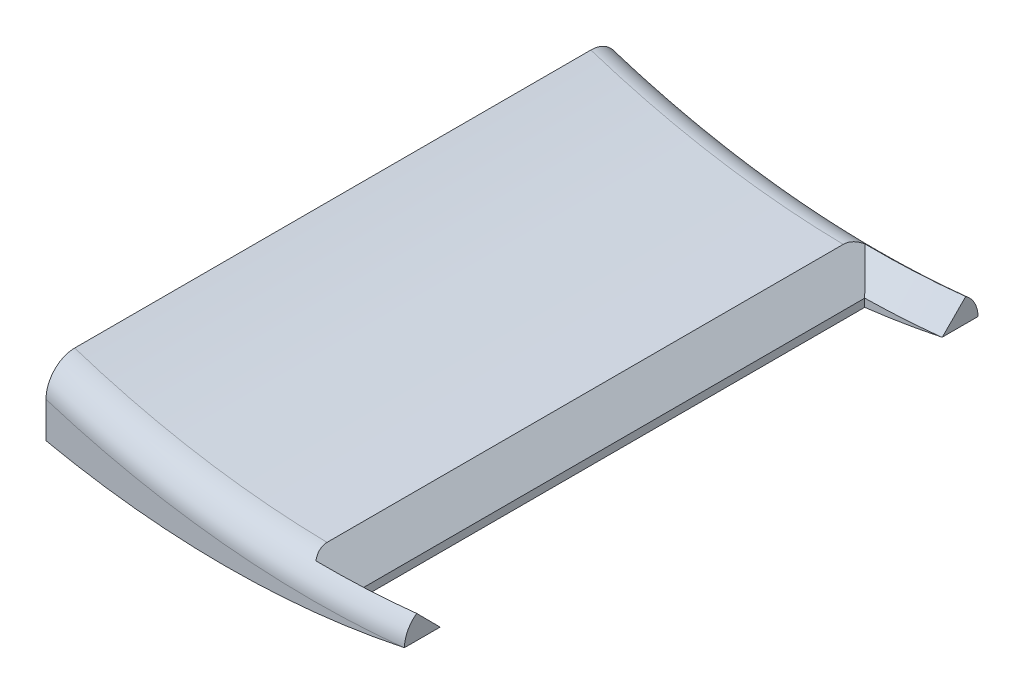
SolidWorks part; units mm, degrees
ref_plane "Front Plane" through (0, 0, 0) normal (0, 0, 1) x (1, 0, 0)
ref_plane "Top Plane" through (0, 0, 0) normal (0, 1, 0) x (1, 0, 0)
ref_plane "Right Plane" through (0, 0, 0) normal (1, 0, 0) x (0, 0, -1)
sketch "Sketch1" plane through (0, 0, 0) normal (0, 0, 1) x (1, 0, 0)
  line L0 (0, 0) -> (0, 5.842)
  line L1 (31.75, 0) -> (31.75, 2.54)
  arc A0 (0, 0) -> (31.75, 0) centre (15.875, 74.528) ccw
  arc A1 (0, 5.842) -> (31.75, 2.54) centre (23.5824, 78.301) ccw
  dimension "D2" = 76.2
  dimension "D1" = 31.75
  dimension "D3" = 2.54
  dimension "D4" = 5.842
extrude "Boss-Extrude1" add sketch "Sketch1" along normal blind 50.8
fillet "Fillet1" radius 2.54 2 edges at (15.7002, 2.5098, 0) (15.7002, 2.5098, 50.8)
ref_plane "Plane1" through (0, 3.81, 0) normal (0, 1, 0) x (1, 0, 0)
sketch "Sketch2" plane through (0, 3.81, 0) normal (0, 1, 0) x (1, 0, 0)
  line L1 (31.75, -48.26) -> (31.75, -2.54) construction
  line L2 (31.75, -3.175) -> (24.892, -3.175)
  line L3 (31.75, -3.175) -> (31.75, -47.625)
  line L4 (31.75, -47.625) -> (24.892, -47.625)
  line L5 (24.892, -3.175) -> (24.892, -47.625)
  point P8 (31.75, -25.4)
  dimension "D1" = 44.45
  dimension "D2" = 6.858
extrude "Cut-Extrude1" cut sketch "Sketch2" against normal blind 38.1
chamfer "Chamfer1" distance 2.54 angle 45 3 edges at (24.892, 2.1123, 25.4) (28.3258, 2.2488, 47.625) (28.3258, 2.2488, 3.175) first distance on face at (24.892, 0.4878, 25.4) first distance on face at (28.3254, 0.84, 47.625) first distance on face at (28.3254, 0.84, 3.175)
